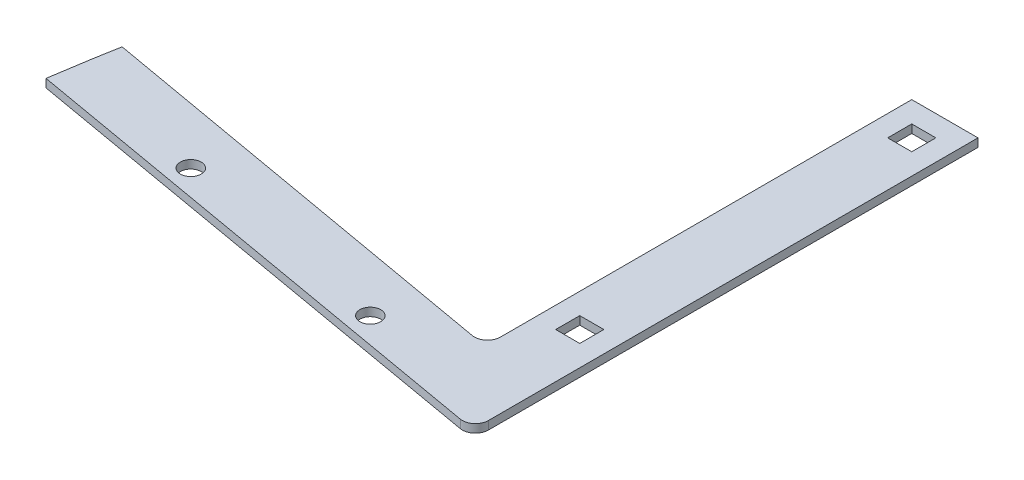
SolidWorks part; units mm, degrees
ref_plane "Front Plane" through (0, 0, 0) normal (0, 0, 1) x (1, 0, 0)
ref_plane "Top Plane" through (0, 0, 0) normal (0, 1, 0) x (1, 0, 0)
ref_plane "Right Plane" through (0, 0, 0) normal (1, 0, 0) x (0, 0, -1)
sketch "Sketch1" plane through (0, 0, 0) normal (0, 1, 0) x (1, 0, 0)
  line L1 (0.0081, 101.8928) -> (12.7081, 101.8928)
  line L2 (0.0081, 101.8928) -> (0.0081, 12.9928)
  line L3 (0.0081, 12.9928) -> (12.7081, 12.9928)
  line L4 (12.7081, 101.8928) -> (12.7081, 12.9928)
  line L6 (4.0481, 97.8528) -> (8.6681, 97.8528)
  line L7 (4.0481, 97.8528) -> (4.0481, 93.2328)
  line L8 (4.0481, 93.2328) -> (8.6681, 93.2328)
  line L9 (8.6681, 97.8528) -> (8.6681, 93.2328)
  line L27 (4.0481, 34.2028) -> (4.0481, 29.5828)
  line L28 (4.0481, 34.2028) -> (8.6681, 34.2028)
  line L29 (8.6681, 34.2028) -> (8.6681, 29.5828)
  line L30 (4.0481, 29.5828) -> (8.6681, 29.5828)
  line L31 (4.0481, 46.9328) -> (4.0481, 42.3128) [skipped]
  line L32 (4.0481, 42.3128) -> (8.6681, 42.3128) [skipped]
  line L33 (8.6681, 46.9328) -> (8.6681, 42.3128) [skipped]
  line L34 (4.0481, 46.9328) -> (8.6681, 46.9328) [skipped]
  line L35 (4.0481, 59.6628) -> (4.0481, 55.0428) [skipped]
  line L36 (4.0481, 55.0428) -> (8.6681, 55.0428) [skipped]
  line L37 (8.6681, 59.6628) -> (8.6681, 55.0428) [skipped]
  line L38 (4.0481, 59.6628) -> (8.6681, 59.6628) [skipped]
  line L39 (4.0481, 72.3928) -> (4.0481, 67.7728) [skipped]
  line L40 (4.0481, 67.7728) -> (8.6681, 67.7728) [skipped]
  line L41 (8.6681, 72.3928) -> (8.6681, 67.7728) [skipped]
  line L42 (4.0481, 72.3928) -> (8.6681, 72.3928) [skipped]
  line L43 (4.0481, 85.1228) -> (4.0481, 80.5028) [skipped]
  line L44 (4.0481, 80.5028) -> (8.6681, 80.5028) [skipped]
  line L45 (8.6681, 85.1228) -> (8.6681, 80.5028) [skipped]
  line L46 (4.0481, 85.1228) -> (8.6681, 85.1228) [skipped]
  dimension "D7" = 6
  dimension "D1" = 12.7
  dimension "D2" = 88.9
  dimension "D3" = 4.62
  dimension "D4" = 4.62
  dimension "D5" = 4.04
  dimension "D6" = 4.04
extrude "Boss-Extrude1" add sketch "Sketch1" along normal blind 1.5875
sketch "Sketch2" plane through (0, 0, 0) normal (0, -1, 0) x (1, 0, 0)
  line L1 (-85.2803, -30.2708) -> (-84.4533, -34.9609)
  line L2 (-84.4533, -34.9609) -> (12.7081, -17.8288)
  line L3 (12.7081, -17.8288) -> (12.7081, -12.9928)
  line L4 (0.0081, -12.9928) -> (0.0081, -101.8928)
  line L5 (0.0081, -101.8928) -> (12.7081, -101.8928)
  line L6 (12.7081, -101.8928) -> (12.7081, -12.9928)
  line L7 (12.7081, -12.9928) -> (0.0081, -12.9928)
  line L8 (0.0081, -12.9928) -> (0.0081, -101.8928)
  line L9 (0.0081, -101.8928) -> (12.7081, -101.8928)
  line L10 (12.7081, -101.8928) -> (12.7081, -12.9928)
  line L11 (12.7081, -12.9928) -> (0.0081, -12.9928)
  line L12 (12.7081, -12.9928) -> (12.7081, -5.0528)
  line L13 (12.7081, -5.0528) -> (-86.5092, -22.4264)
  line L14 (-86.5092, -22.4264) -> (-85.2803, -30.2708)
  circle A0 centre (-57.7386, -21.4177) radius 2
  circle A1 centre (-16.0234, -14.113) radius 2
  line M6 (0.0081, -12.9928) -> (0.0081, -101.8928)
  dimension "D7" = 4
  dimension "D10" = 4
  dimension "D2" = 99.5
  dimension "D3" = 4.7625
  dimension "D4" = 80
  dimension "D5" = 7.94
  dimension "D6" = 7.94
  dimension "D8" = 3.9688
  dimension "D9" = 28.58
  dimension "D11" = 3.9687
  dimension "D12" = 42.35
  dimension "D1" = 0
extrude "Boss-Extrude2" add sketch "Sketch2" against normal up to surface (1.5875 mm away) contours L1 L2 M6 region at (-39.2374, 0, -20.3755) up to face at (6.3581, 1.5875, -57.4428)
fillet "Fillet1" radius 2.5 1 edges at (12.7081, 0.7938, -5.0528)
fillet "Fillet2" radius 2.5 1 edges at (0.0081, 0.7938, -20.0681)
